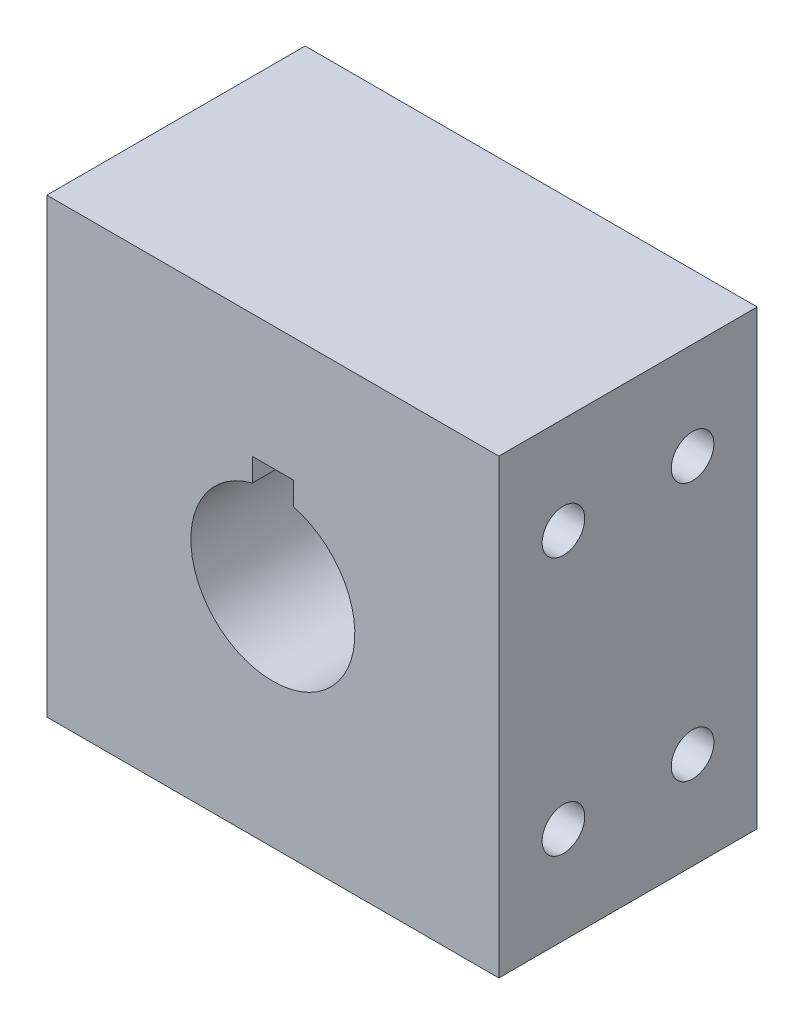
SolidWorks part; units mm, degrees
material "AISI 304"
ref_plane "Front Plane" through (0, 0, 0) normal (0, 0, 1) x (1, 0, 0)
ref_plane "Top Plane" through (0, 0, 0) normal (0, 1, 0) x (1, 0, 0)
ref_plane "Right Plane" through (0, 0, 0) normal (1, 0, 0) x (0, 0, -1)
sketch "Sketch1" plane through (0, 0, 0) normal (0, 0, 1) x (1, 0, 0)
  line L1 (0, 0) -> (-35, 0)
  line L2 (0, 0) -> (0, 35)
  line L3 (0, 35) -> (-35, 35)
  line L4 (-35, 0) -> (-35, 35)
  dimension "D1" = 35
  dimension "D2" = 35
extrude "Boss-Extrude1" add sketch "Sketch1" along normal blind 20
ref_plane "Plane1" through (-17.5, 0, 0) normal (-1, 0, 0) x (0, 0, 1)
sketch "Sketch2" plane through (0, 0, 20) normal (0, 0, 1) x (1, 0, 0)
  line L0 (0, 35) -> (-35, 35) construction
  line L1 (-35, 35) -> (-35, 0) construction
  line L3 (-19.0875, 25.4375) -> (-15.9125, 25.4375)
  line L4 (-19.0875, 25.4375) -> (-19.0875, 22.2625)
  line L5 (-19.0875, 22.2625) -> (-15.9125, 22.2625)
  line L6 (-15.9125, 25.4375) -> (-15.9125, 22.2625)
  circle A0 centre (-17.5, 17.5) radius 6.35
  point P5 (-17.5, 35)
  point P9 (-35, 17.5)
  point P12 (-17.5, 22.2625)
  dimension "D1" = 12.7
  dimension "D2" = 3.175
  dimension "D3" = 3.175
  dimension "D4" = 4.7625
extrude "Cut-Extrude1" cut sketch "Sketch2" against normal through all contours L4 A0 L6 L5 | A0 L6 L3 L4 | L6 A0 L4 L5 region at (-17.5, 24.6093, 20) region at (-17.5, 23.024, 20) region at (-17.5, 17.2811, 20)
hole_wizard "M4x0.7 Tapped Hole1" positions "Sketch3" profile "Sketch4" tap size "M4x0.7" standard "ANSI Metric"
sketch "Sketch3" plane through (-35, 0, 0) normal (-1, 0, 0) x (0, 0, 1)
  line L1 (5, 27.5) -> (15, 27.5)
  line L2 (5, 27.5) -> (5, 7.5)
  line L3 (5, 7.5) -> (15, 7.5)
  line L4 (15, 27.5) -> (15, 7.5)
  line L5 (0, 35) -> (0, 0) construction
  line L6 (20, 35) -> (0, 35) construction
  point P1 (5, 27.5)
  point P2 (15, 7.5)
  point P153 (5, 7.5)
  point P154 (15, 27.5)
  point P168 (0, 17.5)
  point P169 (5, 17.5)
  point P170 (10, 27.5)
  point P173 (10, 35)
  dimension "D1" = 10
  dimension "D2" = 20
sketch "Sketch4" plane through (-35, 27.5, 5) normal (0, 1, 0) x (0, 0, 1)
  line L0 (0, 0) -> (0, 10.9914)
  line L1 (0, 10.9914) -> (1.65, 10)
  line L2 (1.65, 10) -> (1.65, 0)
  line L5 (1.65, 0) -> (0, 0)
  line L10 (0, 10.9914) -> (-1.65, 10) construction
  line L11 (0, -6.35) -> (0, 107.95) construction
  dimension "Tap Drill Dia." = 3.3
  dimension "Tap Drill Depth" = 10
  dimension "Drill Angle" = 118
mirror "Mirror1" about plane through (-17.5, 0, 0) normal (-1, 0, 0) of "M4x0.7 Tapped Hole1"
ref_axis "Axis1" through (-17.5, 17.5, 0) along (0, 0, 1)
